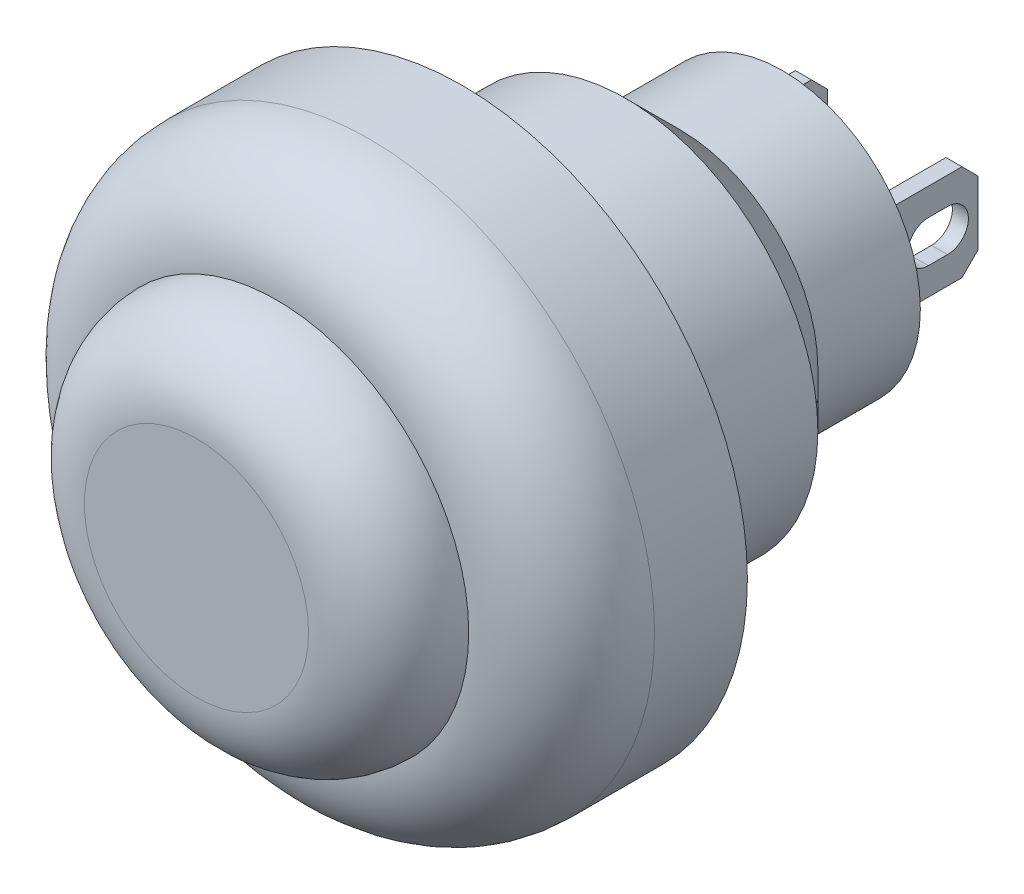
SolidWorks part; units mm, degrees
ref_plane "前视基准面" through (0, 0, 0) normal (0, 0, 1) x (1, 0, 0)
ref_plane "上视基准面" through (0, 0, 0) normal (0, 1, 0) x (1, 0, 0)
ref_plane "右视基准面" through (0, 0, 0) normal (1, 0, 0) x (0, 0, -1)
sketch "草图1" plane through (0, 0, 0) normal (0, 0, 1) x (1, 0, 0)
  circle A0 centre (0, 0) radius 8.9
extrude "凸台-拉伸1" add sketch "草图1" along normal blind 5.8
fillet "圆角2" radius 2.9 1 edges at (8.9, 0, 5.8)
sketch "草图2" plane through (0, 0, 0) normal (0, 0, -1) x (-1, 0, 0)
  circle A0 centre (0, 0) radius 6.75
extrude "凸台-拉伸2" add sketch "草图2" along normal blind 1
sketch "草图3" plane through (0, 0, -1) normal (0, 0, -1) x (-1, 0, 0)
  circle A0 centre (0, 0) radius 6
extrude "凸台-拉伸3" add sketch "草图3" along normal blind 7.5
sketch "草图4" plane through (0, 0, -8.5) normal (0, 0, -1) x (-1, 0, 0)
  circle A0 centre (0, 0) radius 4.3
extrude "凸台-拉伸4" add sketch "草图4" along normal blind 1.5
chamfer "倒角1" distance 3.4 angle 45 1 edges at (-6, 0, -8.5)
sketch "草图5" plane through (0, 0, -10) normal (0, 0, -1) x (-1, 0, 0)
  line L0 (-2.6, 1.5) -> (-2.1, 1.5)
  line L1 (2.1, 0) -> (2.1, 1.5)
  line L2 (2.1, 0) -> (2.1, -1.5)
  line L3 (2.1, -1.5) -> (2.6, -1.5)
  line L4 (2.6, -1.5) -> (2.6, 1.5)
  line L5 (2.6, 1.5) -> (2.1, 1.5)
  line L6 (-2.6, -1.5) -> (-2.1, -1.5)
  line L7 (-2.6, -1.5) -> (-2.6, 1.5)
  line L8 (-2.1, 0) -> (-2.1, -1.5)
  line L9 (-2.1, 0) -> (-2.1, 1.5)
  point P8 (-2.1, -1.5)
  point P9 (-2.1, 1.5)
extrude "凸台-拉伸5" add sketch "草图5" along normal blind 3.5
sketch "草图6" plane through (-2.6, 0, 0) normal (-1, 0, 0) x (0, 0, 1)
  line L4 (-12.55, 0.65) -> (-11.95, 0.65)
  line L5 (-12.55, -0.65) -> (-11.95, -0.65)
  arc A1 (-12.55, 0.65) -> (-12.55, -0.65) centre (-12.55, 0) ccw
  arc A2 (-11.95, -0.65) -> (-11.95, 0.65) centre (-11.95, 0) ccw
extrude "切除-拉伸1" cut sketch "草图6" against normal blind 6.5
chamfer "倒角2" distance 0.5 angle 45 4 edges at (-2.35, -1.5, -13.5) (-2.35, 1.5, -13.5) (2.35, 1.5, -13.5) (2.35, -1.5, -13.5)
sketch "草图7" plane through (0, 0, 5.8) normal (0, 0, 1) x (1, 0, 0)
  circle A0 centre (0, 0) radius 6
extrude "凸台-拉伸6" add sketch "草图7" along normal blind 2.5
fillet "圆角3" radius 2.5 1 edges at (6, 0, 8.3)
